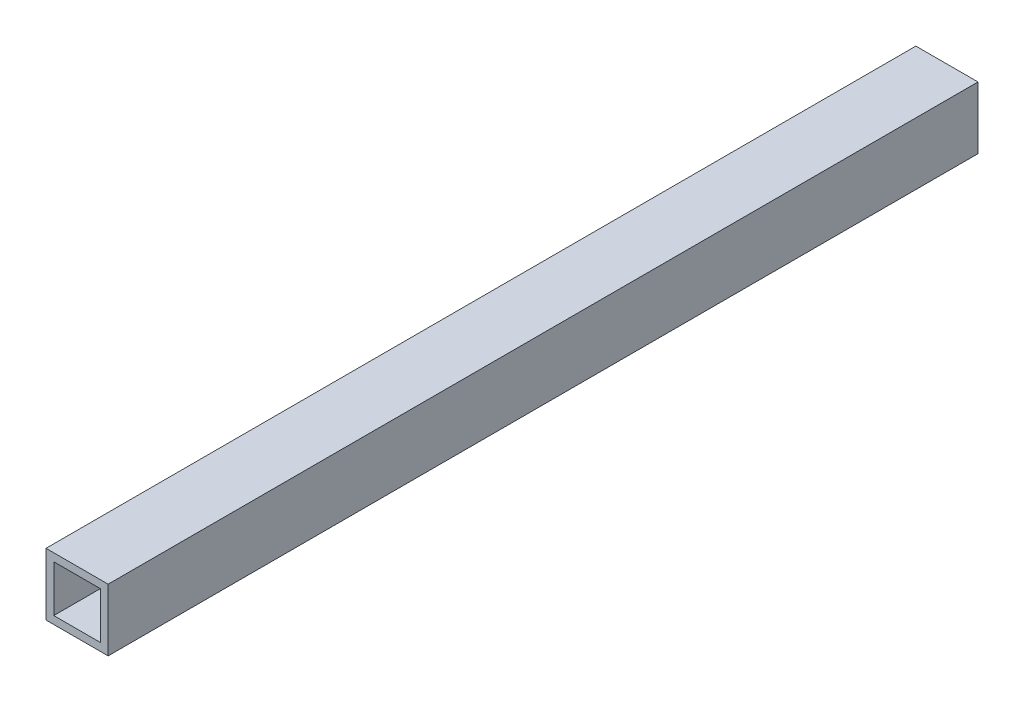
SolidWorks part; units mm, degrees
ref_plane "Front Plane" through (0, 0, 0) normal (0, 0, 1) x (1, 0, 0)
ref_plane "Top Plane" through (0, 0, 0) normal (0, 1, 0) x (1, 0, 0)
ref_plane "Right Plane" through (0, 0, 0) normal (1, 0, 0) x (0, 0, -1)
sketch "Sketch1" plane through (0, 0, 0) normal (0, 0, 1) x (1, 0, 0)
  line L0 (12.7, 0) -> (9.525, 0) construction
  line L1 (-12.7, 0) -> (12.7, 0) construction
  line L2 (0, 12.7) -> (0, -12.7)
  point P7 (0, 0)
sketch "Sketch2" plane through (0, 0, 0) normal (1, 0, 0) x (0, 0, -1)
  line L0 (177.8, 0) -> (-177.8, 0)
  point P4 (0, 0)
  dimension "Length" = 355.6
sketch "Sketch3" plane through (0, 0, 0) normal (0, 0, 1) x (1, 0, 0)
  line L0 (-12.7, 0) -> (12.7, 0) construction
  line L5 (12.7, -12.7) -> (-12.7, -12.7)
  line L6 (12.7, -12.7) -> (12.7, 12.7)
  line L11 (12.7, 12.7) -> (-12.7, 12.7)
  line L12 (-12.7, -12.7) -> (-12.7, 12.7)
  line L14 (12.7, -12.7) -> (-12.7, 12.7) construction
  line L15 (12.7, 12.7) -> (-12.7, -12.7) construction
  line L16 (9.525, -9.525) -> (-9.525, -9.525)
  line L17 (9.525, -9.525) -> (9.525, 9.525)
  line L18 (9.525, 9.525) -> (-9.525, 9.525)
  line L19 (-9.525, -9.525) -> (-9.525, 9.525)
  line L20 (9.525, -9.525) -> (-9.525, 9.525) construction
  line L21 (9.525, 9.525) -> (-9.525, -9.525) construction
  point P0 (0, 0)
  point P5 (0, 0)
  point P13 (9.525, -12.7)
  dimension "D1" = 3.175
extrude "Boss-Extrude1" add sketch "Sketch3" along normal up to vertex (177.8 mm away) and the other way up to vertex (177.8 mm away) up to point (0, 0, 177.8) other way up to point (0, 0, -177.8)
sketch "Sketch5" plane through (0, 0, 0) normal (1, 0, 0) x (0, 0, -1)
  line L0 (-177.8, 0) -> (177.8, 0) construction
  line L3 (-177.8, -12.7) -> (-177.8, 12.7) construction
  line L4 (177.8, -12.7) -> (177.8, 12.7) construction
  point P6 (-149.225, 0)
  point P7 (-139.7, 0)
  point P8 (139.7, 0)
  point P10 (149.225, 0)
  dimension "D1" = 28.575
  dimension "D2" = 38.1
  dimension "D3" = 28.575
  dimension "D4" = 38.1
equation "\"D1@Sketch3\"=\"Wall thickness@Sketch1\""
equation "\"D1@Sketch5\"=\"Width@Sketch1\"*1.125"
equation "\"D2@Sketch5\"=\"Width@Sketch1\"*1.5"
equation "\"D3@Sketch5\"=\"D1@Sketch5\""
equation "\"D4@Sketch5\"=\"D2@Sketch5\""
equation "\"D2@Sketch3\"=\"Wall Thickness@Sketch1\""
